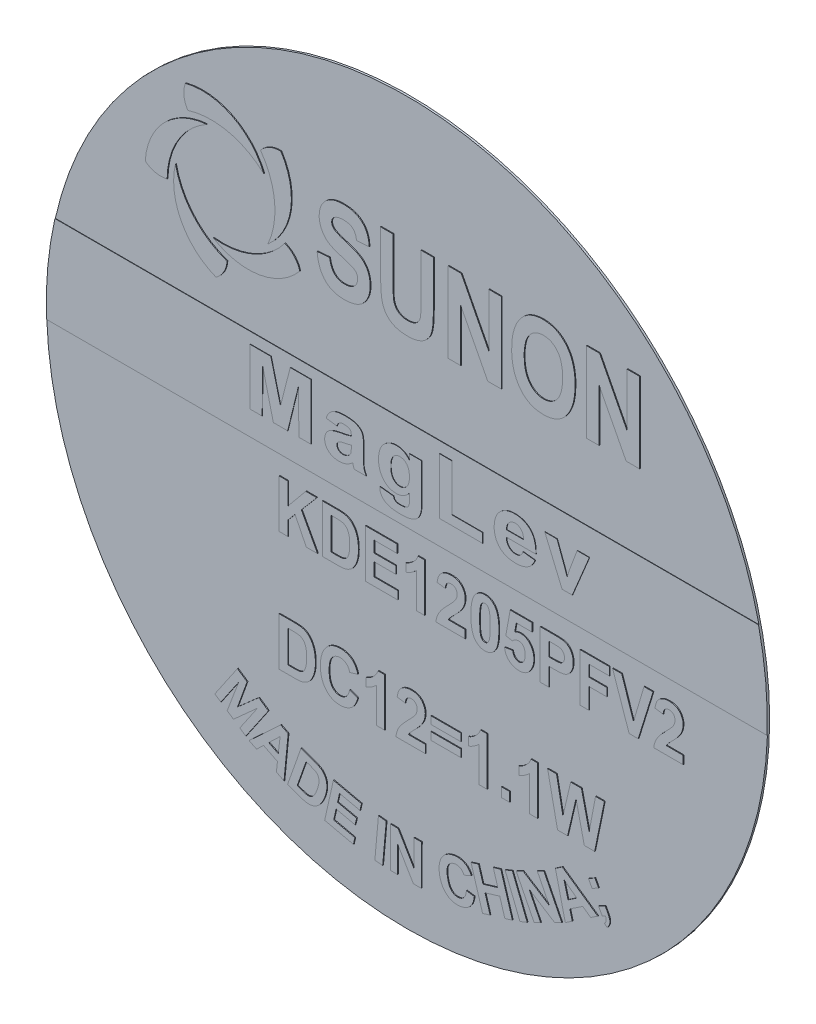
SolidWorks part; units mm, degrees
material "PET"
ref_plane "Front" through (0, 0, 0) normal (0, 0, 1) x (1, 0, 0)
ref_plane "Top" through (0, 0, 0) normal (0, 1, 0) x (1, 0, 0)
ref_plane "Right" through (0, 0, 0) normal (1, 0, 0) x (0, 0, -1)
sketch "Эскиз1" plane through (0, 0, 0) normal (0, 0, 1) x (1, 0, 0)
  circle A0 centre (0, 0) radius 9
  dimension "D1" = 18
extrude "Бобышка-Вытянуть1" add sketch "Эскиз1" along normal blind 0.05
sketch "Эскиз2" plane through (0, 0, 0.05) normal (0, 0, 1) x (1, 0, 0)
  arc A0 (-4.8588, -6.2452) -> (4.8833, -6.2452) centre (0.0123, -0.0965) ccw construction
  arc A2 (-5.5151, 6.5319) -> (-3.5562, 5.5539) centre (-5.0958, 4.9209) cw
  arc A4 (-5.4535, 5.9772) -> (-3.5562, 5.5539) centre (-4.8709, 4.1247) cw
  arc A5 (-5.5151, 6.5319) -> (-5.4535, 5.9772) centre (-4.9377, 6.3153) ccw
  circle A6 centre (-4.5148, 4.7517) radius 1.25 construction
  arc A7 (-3.1308, 6.2532) -> (-3.4556, 4.0879) centre (-4.5334, 5.3566) cw
  arc A8 (-3.1308, 6.2532) -> (-3.6393, 6.0232) centre (-3.1584, 5.6371) ccw
  arc A9 (-3.6393, 6.0232) -> (-3.4556, 4.0879) centre (-5.2212, 4.8967) cw
  arc A10 (-2.6591, 3.8995) -> (-4.8188, 3.5392) centre (-3.9453, 4.9563) cw
  arc A12 (-2.6591, 3.8995) -> (-3.035, 4.312) centre (-3.2536, 3.7353) ccw
  arc A15 (-3.035, 4.312) -> (-4.8188, 3.5392) centre (-4.5952, 5.4683) cw
  arc A16 (-4.7519, 2.7235) -> (-5.7619, 4.6662) centre (-4.1442, 4.2733) cw
  arc A17 (-4.7519, 2.7235) -> (-4.4757, 3.2084) centre (-5.0917, 3.2381) ccw
  arc A18 (-4.4757, 3.2084) -> (-5.7619, 4.6662) centre (-3.8581, 5.0496) cw
  arc A19 (-6.517, 4.3504) -> (-4.9815, 5.9113) centre (-4.8553, 4.2514) cw
  arc A20 (-6.517, 4.3504) -> (-5.9704, 4.2376) centre (-6.1326, 4.8327) ccw
  arc A21 (-5.9704, 4.2376) -> (-4.9815, 5.9113) centre (-4.0285, 4.2192) cw
  text T0 "SUNON" font "Arial Narrow" height 2
  text T1 "KDE1205PFV2\r\nDC12=1.1W" font "Arial Narrow" height 1.2
  text T2 "MADE IN CHINA;)" font "Arial Narrow" height 1
  text T3 "MagLev" font "Arial" height 1.4
  point P40 (-4.5148, 4.7517)
  dimension "D1" = 2.5
  dimension "D2" = 5
extrude "Бобышка-Вытянуть2" add sketch "Эскиз2" along normal blind 0.02
sketch "Эскиз3" plane through (0, 0, 0.05) normal (0, 0, 1) x (1, 0, 0)
  line L0 (-8.7818, 1.9697) -> (8.7818, 1.9697)
  line L1 (-10.1071, 1.9697) -> (9.8757, 1.9697) construction
  line L2 (-10.1071, 1.9697) -> (-10.1071, -0.3149) construction
  line L3 (-10.1071, -0.3149) -> (9.8757, -0.3149) construction
  line L4 (9.8757, 1.9697) -> (9.8757, -0.3149) construction
  line L5 (-0.1157, -0.3149) -> (-0.1157, 1.9697) construction
  line L6 (-10.1071, 0.8274) -> (9.8757, 0.8274) construction
  line L7 (-8.9945, -0.3149) -> (8.9945, -0.3149)
  circle A0 centre (0, 0) radius 9 construction
  arc A1 (-8.7818, 1.9697) -> (-8.9945, -0.3149) centre (0, 0) ccw
  arc A2 (8.7818, 1.9697) -> (8.9945, -0.3149) centre (0, 0) cw
  point P0 (-0.1157, 0.8274)
  dimension "D1" = 2.2846
  dimension "D2" = 19.9828
extrude "Бобышка-Вытянуть3" add sketch "Эскиз3" along normal blind 0.01
